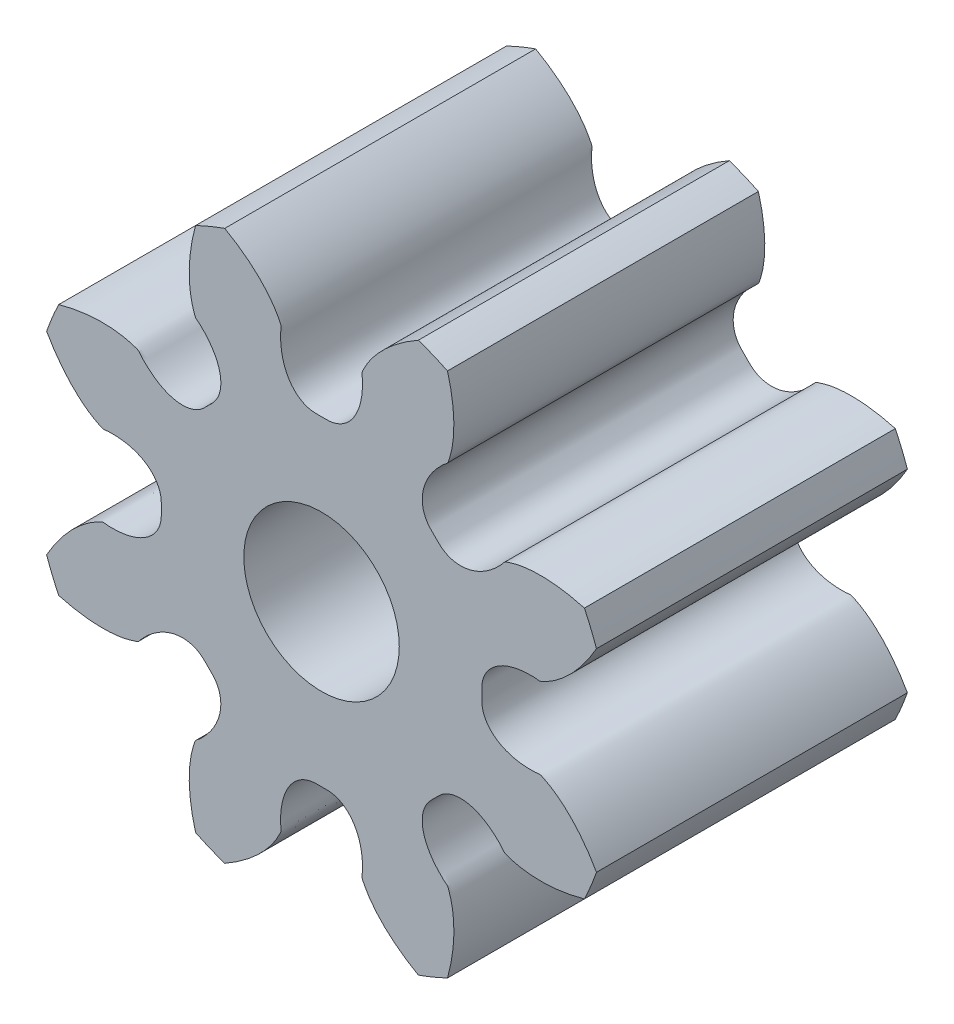
SolidWorks part; units mm, degrees
ref_plane "Alzado" through (0, 0, 0) normal (0, 0, 1) x (1, 0, 0)
ref_plane "Planta" through (0, 0, 0) normal (0, 1, 0) x (1, 0, 0)
ref_plane "Vista lateral" through (0, 0, 0) normal (1, 0, 0) x (0, 0, -1)
ref_axis "Eje1" through (0, 0, 55) along (0, 0, -1)
sketch "SketchRevolveSpur01" plane through (0, 0, 0) normal (1, 0, 0) x (0, 0, -1)
  line L0 (0, 0) -> (1, 0) construction
  line L1 (-0.25, 0) -> (-0.25, 0.9375)
  line L2 (-0.25, 0.9375) -> (0.75, 0.9375)
  line L3 (0.75, 0.9375) -> (0.75, 0)
  line L4 (0.75, 0) -> (-0.25, 0)
  dimension "D1" = 1
revolve "Spur01" add sketch "SketchRevolveSpur01" angle 360 about L0
sketch "SketchToothSpur01" plane through (0, 0, 0) normal (0, 0, 1) x (1, 0, 0)
  arc A0 (0.8903, 0.3224) -> (0.8903, -0.3224) centre (0, 0) cw
  spline S0 degree 3 poles (0.8903, -0.3224) (0.8779, -0.2992) (0.86, -0.2702) (0.835, -0.2372) (0.8209, -0.2203) (0.8071, -0.2051) (0.7936, -0.1915) (0.7805, -0.1795) (0.768, -0.169) (0.7562, -0.16) (0.7451, -0.1523) (0.7349, -0.1458) (0.7257, -0.1405) (0.7153, -0.1355) (0.7028, -0.1279) (0.6887, -0.1318) (0.6772, -0.1317) (0.6684, -0.1317) (0.6598, -0.1314) (0.6514, -0.1308) (0.6431, -0.13) (0.6351, -0.1289) (0.6271, -0.1275) (0.6194, -0.1259) (0.6118, -0.124) (0.6045, -0.1218) (0.5973, -0.1194) (0.5903, -0.1166) (0.5835, -0.1136) (0.5769, -0.1103) (0.5705, -0.1068) (0.5643, -0.1029) (0.5584, -0.0986) (0.5527, -0.0941) (0.5472, -0.0892) (0.542, -0.0839) (0.5372, -0.0783) (0.5327, -0.0723) (0.5286, -0.0659) (0.5249, -0.0591) (0.5218, -0.052) (0.5192, -0.0445) (0.5172, -0.0367) (0.5159, -0.0287) (0.5154, -0.0216) (0.5153, -0.012) (0.5159, 0) (0.5153, 0.012) (0.5154, 0.0216) (0.5159, 0.0287) (0.5172, 0.0367) (0.5192, 0.0445) (0.5218, 0.052) (0.5249, 0.0591) (0.5286, 0.0659) (0.5327, 0.0723) (0.5372, 0.0783) (0.542, 0.0839) (0.5472, 0.0892) (0.5527, 0.0941) (0.5584, 0.0986) (0.5643, 0.1029) (0.5705, 0.1068) (0.5769, 0.1103) (0.5835, 0.1136) (0.5903, 0.1166) (0.5973, 0.1194) (0.6045, 0.1218) (0.6118, 0.124) (0.6194, 0.1259) (0.6271, 0.1275) (0.6351, 0.1289) (0.6431, 0.13) (0.6514, 0.1308) (0.6598, 0.1314) (0.6684, 0.1317) (0.6772, 0.1317) (0.6887, 0.1318) (0.7028, 0.1279) (0.7153, 0.1355) (0.7257, 0.1405) (0.7349, 0.1458) (0.7451, 0.1523) (0.7562, 0.16) (0.768, 0.169) (0.7805, 0.1795) (0.7936, 0.1915) (0.8071, 0.2051) (0.8209, 0.2203) (0.835, 0.2372) (0.86, 0.2702) (0.8779, 0.2992) (0.8903, 0.3224) knots 0 0 0 0 0.073215 0.094985 0.115436 0.134568 0.15238 0.168873 0.184046 0.1979 0.210435 0.22165 0.231545 0.240121 0.254211 0.270122 0.278422 0.28657 0.29457 0.302428 0.31015 0.31774 0.325207 0.332558 0.3398 0.346942 0.353995 0.360969 0.367876 0.374729 0.381542 0.388328 0.395105 0.401889 0.408696 0.415544 0.422448 0.429425 0.436487 0.443642 0.450898 0.458253 0.465701 0.473229 0.48082 0.485566 0.5 0.514434 0.51918 0.526771 0.534299 0.541747 0.549102 0.556358 0.563513 0.570575 0.577552 0.584456 0.591304 0.598111 0.604895 0.611672 0.618458 0.625271 0.632124 0.639031 0.646005 0.653058 0.6602 0.667442 0.674793 0.68226 0.68985 0.697572 0.70543 0.71343 0.721578 0.729878 0.745789 0.759879 0.768455 0.77835 0.789565 0.8021 0.815954 0.831127 0.84762 0.865432 0.884564 0.905015 0.926785 1 1 1 1
extrude "ToothExtrudeCutSpur01" cut sketch "SketchToothSpur01" against normal up to next and the other way blind 0.25
pattern_circular "PatternSpur01" count 8 every 45 about axis through (0, 0, 55) along (0, 0, -1) of "ToothExtrudeCutSpur01"
sketch "AuxiliarySketchSpur01" plane through (0, 0, 0) normal (0, 0, 1) x (1, 0, 0)
  circle A0 centre (0, 0) radius 0.75 construction
  circle A1 centre (0, 0) radius 0.7048 construction
  circle A2 centre (0, 0) radius 0.7742 construction
  circle A3 centre (0, 0) radius 0.9375 construction
  circle A4 centre (0, 0) radius 0.5156 construction
  dimension "PitchDiameter" = 1.5
  dimension "BaseDiameter" = 1.4095
  dimension "FormDiameter" = 1.5485
  dimension "MajorDiameter" = 1.875
  dimension "MinorDiameter" = 1.0313
sketch "Croquis5" plane through (0, 0, 0.25) normal (0, 0, 1) x (1, 0, 0)
  circle A0 centre (0, 0) radius 0.25
  dimension "D1" = 0.5
extrude "Cortar-Extruir2" cut sketch "Croquis5" against normal up to next
